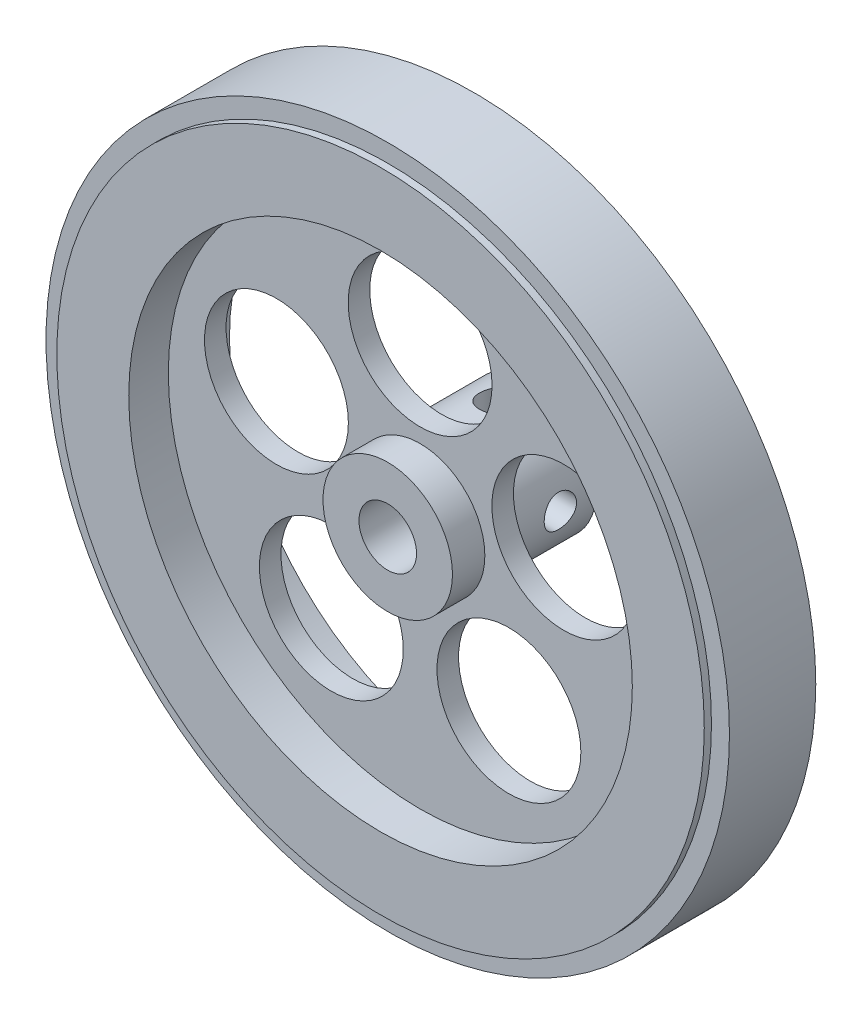
SolidWorks part; units mm, degrees
material "6061-T6 (SS)"
ref_plane "정면" through (0, 0, 0) normal (0, 0, 1) x (1, 0, 0)
ref_plane "윗면" through (0, 0, 0) normal (0, 1, 0) x (1, 0, 0)
ref_plane "우측면" through (0, 0, 0) normal (1, 0, 0) x (0, 0, -1)
sketch "스케치1" plane through (0, 0, 0) normal (0, 0, 1) x (1, 0, 0)
  circle A0 centre (0, 0) radius 4
  circle A1 centre (0, 0) radius 9
  dimension "D1" = 8
  dimension "D2" = 18
extrude "보스-돌출1" add sketch "스케치1" along normal blind 20
ref_plane "평면1" through (0, 0, 14) normal (0, 0, 1) x (1, 0, 0)
sketch "스케치2" plane through (0, 0, 14) normal (0, 0, 1) x (1, 0, 0)
  circle A0 centre (0, 0) radius 45
  dimension "D1" = 90
extrude "보스-돌출2" add sketch "스케치2" along normal blind 1.5 and the other way blind 1.5
extrude "컷-돌출2" cut sketch "스케치1<2>" along normal through all both and the other way through all contours A0 region at (0, 0, 0)
sketch "스케치1<2>" plane through (0, 0, 0) normal (0, 0, 1) x (1, 0, 0) same geometry as "스케치1"
sketch "스케치3" plane through (0, 0, 15.5) normal (0, 0, 1) x (1, 0, 0)
  circle A0 centre (0, 21) radius 10
  circle A1 centre (19.9722, 6.4894) radius 10
  circle A2 centre (12.3435, -16.9894) radius 10
  circle A3 centre (-12.3435, -16.9894) radius 10
  circle A4 centre (-19.9722, 6.4894) radius 10
  point P13 (0, 0)
  dimension "D1" = 20
  dimension "D2" = 21
  dimension "D3" = 5
extrude "컷-돌출3" cut sketch "스케치3" against normal through all both
sketch "스케치5" plane through (0, 0, 14) normal (0, 0, 1) x (1, 0, 0)
  circle A0 centre (0, 0) radius 45
  circle A1 centre (0, 0) radius 35
  dimension "D1" = 10
extrude "보스-돌출3" add sketch "스케치5" along normal blind 7 and the other way blind 7
sketch "스케치6" plane through (0, 0, 14) normal (0, 0, 1) x (1, 0, 0)
  circle A0 centre (0, 0) radius 45
  circle A1 centre (0, 0) radius 47.5
  dimension "D1" = 95
extrude "보스-돌출4" add sketch "스케치6" along normal blind 6 and the other way blind 6
hole_wizard "M4 여유 구멍1" positions "스케치8" profile "스케치9" hole size "M4" standard "HASCO Metric"
sketch "스케치8" plane through (0, 0, 0) normal (0, 1, 0) x (1, 0, 0)
  line L0 (9, 0) -> (-9, 0) construction
  point P0 (0, -5)
  dimension "D1" = 5
sketch "스케치9" plane through (0, 0, 5) normal (1, 0, 0) x (0, 0, -1)
  line L0 (0, 0) -> (0, 31.3519)
  line L1 (0, 31.3519) -> (2.25, 30)
  line L2 (2.25, 30) -> (2.25, 0)
  line L5 (2.25, 0) -> (0, 0)
  line L10 (0, 31.3519) -> (-2.25, 30) construction
  line L11 (0, -6.35) -> (0, 107.95) construction
  dimension "구멍 지름" = 4.5
  dimension "구멍 깊이" = 30
  dimension "드릴 각도" = 118
hole_wizard "M4 여유 구멍2" positions "스케치11" profile "스케치12" hole size "M4" standard "HASCO Metric"
sketch "스케치11" plane through (0, 0, 0) normal (1, 0, 0) x (0, 0, -1)
  line L0 (0, -4) -> (0, 4) construction
  point P0 (-5, 0)
  dimension "D1" = 5
sketch "스케치12" plane through (0, 0, 5) normal (0, 1, 0) x (0, 0, 1)
  line L0 (0, 0) -> (0, 31.3519)
  line L1 (0, 31.3519) -> (2.25, 30)
  line L2 (2.25, 30) -> (2.25, 0)
  line L5 (2.25, 0) -> (0, 0)
  line L10 (0, 31.3519) -> (-2.25, 30) construction
  line L11 (0, -6.35) -> (0, 107.95) construction
  dimension "구멍 지름" = 4.5
  dimension "구멍 깊이" = 30
  dimension "드릴 각도" = 118
